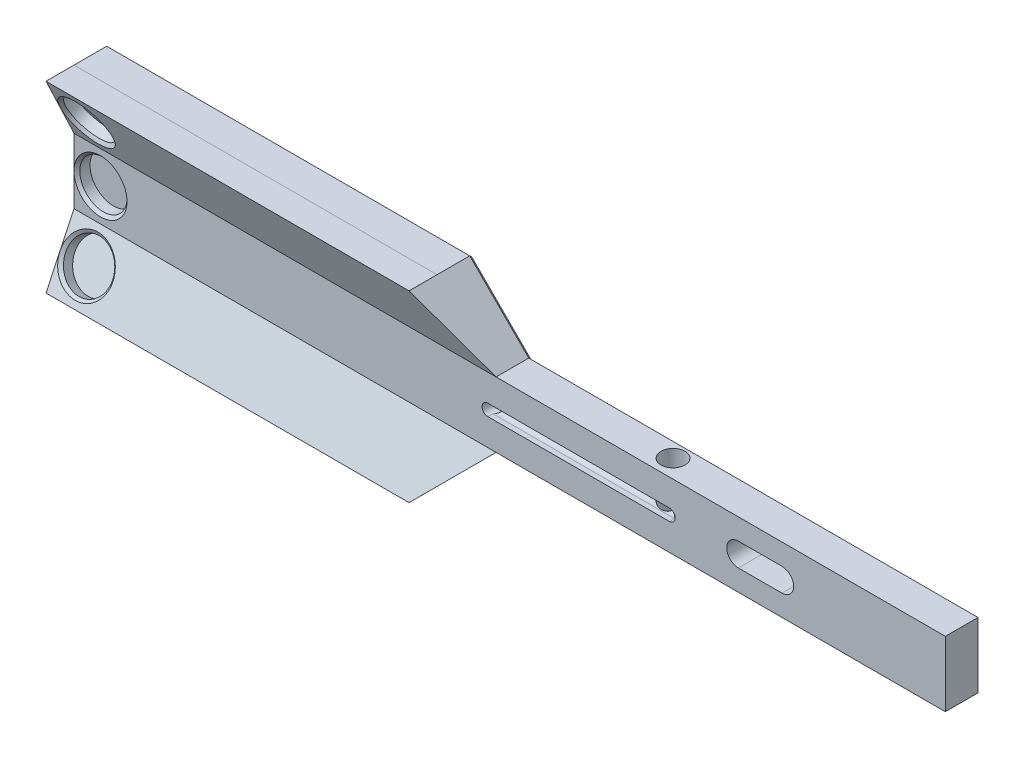
SolidWorks part; units mm, degrees
ref_plane "Front" through (0, 0, 0) normal (0, 0, 1) x (1, 0, 0)
ref_plane "Top" through (0, 0, 0) normal (0, 1, 0) x (1, 0, 0)
ref_plane "Right" through (0, 0, 0) normal (1, 0, 0) x (0, 0, -1)
sketch "Sketch1" plane through (0, 0, 0) normal (0, 0, 1) x (1, 0, 0)
  line L1 (60, -4.5) -> (-60, -4.5)
  line L2 (60, -4.5) -> (60, 4.5)
  line L3 (60, 4.5) -> (-60, 4.5)
  line L4 (-60, -4.5) -> (-60, 4.5)
  line L5 (60, -4.5) -> (-60, 4.5) construction
  line L6 (60, 4.5) -> (-60, -4.5) construction
  point P0 (0, 0)
  dimension "D1" = 9
  dimension "D2" = 120
extrude "Boss-Extrude1" add sketch "Sketch1" along normal blind 5
sketch "Sketch2" plane through (0, 4.5, 0) normal (0, 1, 0) x (1, 0, 0)
  line L0 (60, -5) -> (60, 0) construction
  line L2 (60, 0) -> (-60, 0) construction
  circle A0 centre (20, -2.5) radius 1.65
  dimension "D3" = 3.3
  dimension "D1" = 2.5
  dimension "D2" = 40
sketch "Sketch4" plane through (0, 0, 5) normal (0, 0, 1) x (1, 0, 0)
  line L0 (31.5, 0) -> (37.5, 0) construction
  line L1 (31.5, 1.6) -> (37.5, 1.6)
  line L2 (31.5, -1.6) -> (37.5, -1.6)
  arc A0 (31.5, 1.6) -> (31.5, -1.6) centre (31.5, 0) ccw
  arc A1 (37.5, -1.6) -> (37.5, 1.6) centre (37.5, 0) ccw
  point P2 (34.5, 0)
  dimension "D1" = 1.6
  dimension "D2" = 34.5
  dimension "D3" = 6
extrude "Cut-Extrude1" cut sketch "Sketch4" against normal blind 5
sketch "Sketch8" plane through (0, 0, 0) normal (0, 0, -1) x (-1, 0, 0)
  line L0 (60, 4.5) -> (60, -4.5) construction
  line L1 (60, 12.63) -> (10, 12.63)
  line L2 (60, 12.63) -> (60, -12.63)
  line L3 (60, -12.63) -> (10, -12.63)
  line L4 (10, 12.63) -> (10, -12.63)
  line L6 (-60, 4.5) -> (60, 4.5) construction
  dimension "D1" = 25.26
  dimension "D2" = 8.13
  dimension "D3" = 50
extrude "Boss-Extrude3" add sketch "Sketch8" against normal up to surface (5 mm away) up to face at (34.5, 0, 5)
sketch "Sketch9" plane through (-60, 0, 0) normal (-1, 0, 0) x (0, 0, 1)
  line L0 (5, 12.63) -> (5, -12.63) construction
  line L1 (5, 12.6327) -> (8.8548, 12.6327)
  line L2 (8.8548, 12.6327) -> (5, 4.5)
  line L3 (5, 4.5) -> (5, 12.6327)
  line L4 (-3.9634, 0) -> (12.9509, 0) construction
  line L5 (8.8548, -12.6327) -> (5, -4.5)
  line L6 (5, -12.6327) -> (8.8548, -12.6327)
  line L7 (5, -4.5) -> (5, -12.6327)
  circle A0 centre (25, 0) radius 20 construction
  dimension "D1" = 40
  dimension "D2" = 9
  dimension "D3" = 9
extrude "Boss-Extrude4" add sketch "Sketch9" against normal up to surface (50 mm away) up to face at (-10, 8.565, 2.5)
chamfer "Chamfer4" distance 8.13 2 edges at (-10, 4.5, 2.5) (-10, -4.5, 2.5)
chamfer "Chamfer1" distance 0.5 angle 45 12 edges at (60, 0, 0) (29.065, 4.5, 0) (-60, 0, 0) (29.065, -4.5, 0) (39.1, 0, 0) (34.5, -1.6, 0) (29.9, 0, 0) (34.5, 1.6, 0) (-35, 12.63, 0) (-35, -12.63, 0) (-5.935, 8.565, 0) (-5.935, -8.565, 0)
sketch "Sketch10" plane through (-60, 0, 0) normal (-1, 0, 0) x (0, 0, 1)
  line L0 (5, 4.5) -> (5, -4.5) construction
  line L1 (5, 4.5) -> (8.8548, 12.6327) construction
  line L2 (8.8548, -12.6327) -> (5, -4.5) construction
  circle A0 centre (25, 0) radius 20
sketch "Sketch11" plane through (0, 0, 5) normal (0, 0, 1) x (1, 0, 0)
  line L2 (-60, 4.5) -> (-60, -4.5) construction
  circle A0 centre (-56.35, 0) radius 3.25
  dimension "D1" = 6.5
  dimension "D2" = 3.65
extrude "Cut-Extrude3" cut sketch "Sketch11" against normal blind 1.8
sketch "Sketch12" plane through (0, -1.1096, 2.341) normal (0, -0.4283, 0.9036) x (1, 0, 0)
  line L1 (-10, 15.2079) -> (-60, 15.2079) construction
  line L2 (-60, 30.7079) -> (-60, -9.2921) construction
  circle A0 centre (-56.35, 10.7079) radius 3.25
  dimension "D1" = 6.5
  dimension "D2" = 4.5
  dimension "D3" = 3.65
extrude "Cut-Extrude4" cut sketch "Sketch12" against normal blind 1.8
mirror "Mirror2" about plane through (0, 0, 0) normal (0, 1, 0) of "Cut-Extrude4"
chamfer "Chamfer2" distance 0.4 angle 45 3 edges at (-53.1, 0, 5) (-56.35, -5.6295, 5.5354) (-56.35, 5.6295, 5.5354)
ref_plane "Plane1" through (-56, 0, 0) normal (-1, 0, 0) x (0, 0, 1)
extrude "Cut-Extrude5" cut sketch "Sketch2" against normal blind 10
sketch "Sketch13" plane through (60, 0, 0) normal (1, 0, 0) x (0, 0, -1)
  line L0 (-6, 0.8) -> (-4.3, 0.8)
  line L1 (-4.3, -0.8) -> (-6, -0.8)
  line L2 (-6, -0.8) -> (-6, 0.8)
  line L3 (-5, -4.5) -> (-5, 4.5) construction
  arc A0 (-4.3, 0.8) -> (-4.3, -0.8) centre (-4.3, 0) cw
  point P7 (0, 0)
  point P8 (0, 0)
  dimension "D1" = 0.8
  dimension "D2" = 0.7
  dimension "D3" = 1
  dimension "D5" = 1.6
extrude "Cut-Extrude6" cut sketch "Sketch13" against normal blind 25 from offset 38 offset against normal yes
sketch "Sketch14" plane through (22, 0, 0) normal (-1, 0, 0) x (0, 0, 1)
  circle A0 centre (4.2, 0) radius 0.8
  point P2 (0, 0)
  dimension "D2" = 1.6
  dimension "D1" = 0.8
ref_plane "Plane2" through (9.5, 0, 0) normal (-1, 0, 0) x (0, 0, 1)
ref_plane "Plane3" through (29.9, 0, 0) normal (1, 0, 0) x (0, 0, -1)
ref_plane "Plane4" through (27.9, 0, 0) normal (1, 0, 0) x (0, 0, -1)
sketch "Sketch15" plane through (27.9, 0, 0) normal (1, 0, 0) x (0, 0, -1)
  circle A0 centre (-2.2, 0) radius 0.85
  point P2 (0, 0)
  dimension "D1" = 1.7
  dimension "D2" = 2
sketch "Sketch16" plane through (-3, 0, 0) normal (-1, 0, 0) x (0, 0, 1)
  line L1 (5, 4.5) -> (5, 0) construction
  circle A0 centre (4.2, 0) radius 0.8
  point P4 (0, 0)
  dimension "D1" = 1.6
  dimension "D2" = 0.8
sketch "Sketch17" plane through (0, 0, 5) normal (0, 0, 1) x (1, 0, 0)
  line L0 (-3, 0.8) -> (-3, -0.8) construction
  line L1 (22, 0.8) -> (22, -0.8) construction
  circle A0 centre (-3, 0) radius 0.8
  circle A1 centre (22, 0) radius 0.8
  point P7 (22, 0)
  dimension "D1" = 1.6
extrude "Cut-Extrude7" cut sketch "Sketch17" against normal blind 25
